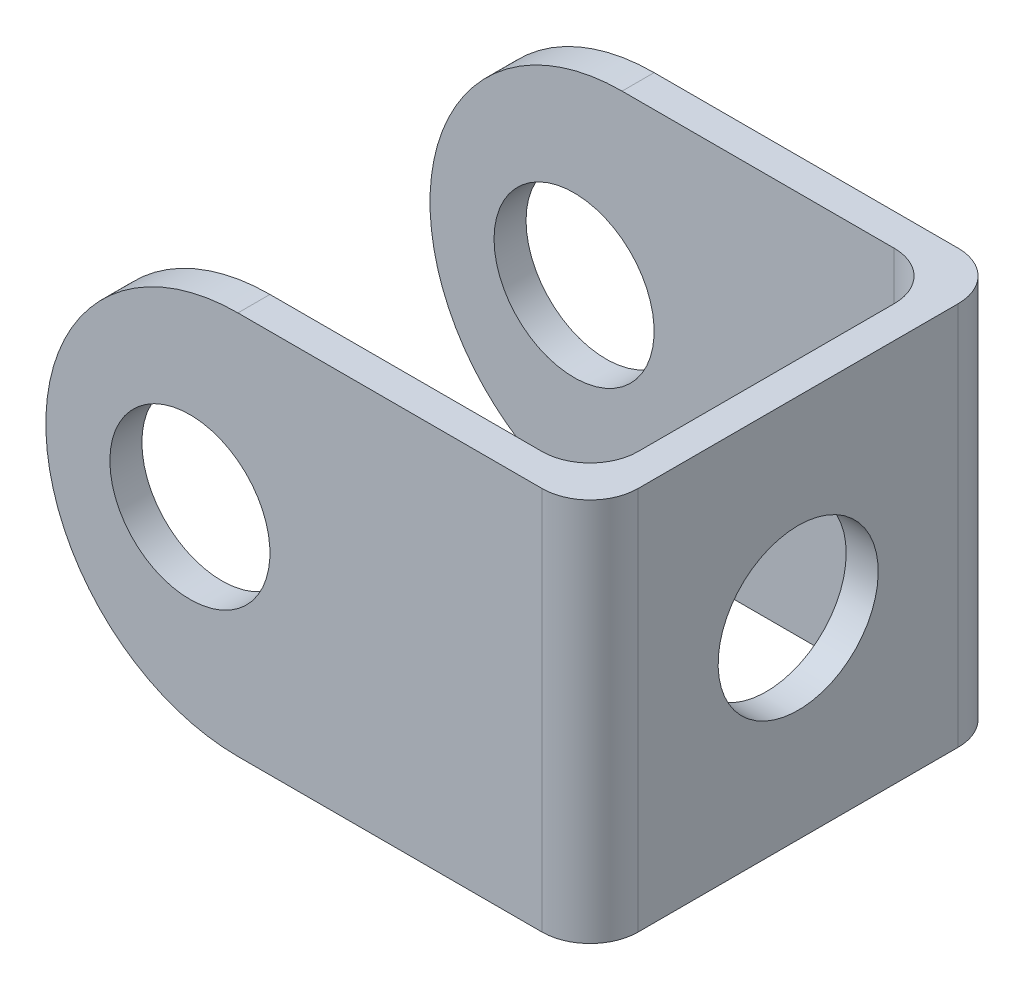
SolidWorks part; units mm, degrees
material "1023 Arkusz stali węglowej (SS)"
ref_plane "Płaszczyzna przednia" through (0, 0, 0) normal (0, 0, 1) x (1, 0, 0)
ref_plane "Płaszczyzna górna" through (0, 0, 0) normal (0, 1, 0) x (1, 0, 0)
ref_plane "Płaszczyzna prawa" through (0, 0, 0) normal (1, 0, 0) x (0, 0, -1)
sketch "Szkic1" plane through (0, 0, 0) normal (0, 0, 1) x (1, 0, 0)
  line L0 (3, 12) -> (25, 12)
  line L1 (3, -12) -> (25, -12)
  line L2 (25, 12) -> (25, -12)
  circle A0 centre (0, 0) radius 5
  arc A1 (3, 12) -> (3, -12) centre (3, 0) ccw
  dimension "D1" = 10
  dimension "D2" = 24
  dimension "D3" = 3
  dimension "D4" = 25
extrude "Dodanie-wyciągnięcie1" add sketch "Szkic1" along normal blind 26
sketch "Szkic2" plane through (0, 12, 0) normal (0, 1, 0) x (1, 0, 0)
  line L0 (25, -26) -> (3, -26) construction
  line L1 (23, -24) -> (-18.5755, -24)
  line L2 (23, -24) -> (23, -2)
  line L3 (23, -2) -> (-18.5755, -2)
  line L4 (-18.5755, -24) -> (-18.5755, -2)
  line L5 (25, 0) -> (3, 0) construction
  line L6 (25, -26) -> (25, 0) construction
  dimension "D1" = 2
  dimension "D2" = 2
  dimension "D3" = 2
extrude "Wytnij-wyciągnięcie1" cut sketch "Szkic2" against normal through all
fillet "Zaokrąglenie1" radius 3 4 edges at (23, 0, 24) (23, 0, 2) (25, 0, 0) (25, 0, 26)
sketch "Szkic3" plane through (25, 0, 0) normal (1, 0, 0) x (0, 0, -1)
  line L0 (-23, 12) -> (-3, 12) construction
  line L1 (0, -12) -> (0, 12) construction
  circle A0 centre (-13, 0) radius 5
  dimension "D1" = 12
  dimension "D3" = 10
  dimension "D2" = 13
extrude "Wytnij-wyciągnięcie2" cut sketch "Szkic3" against normal through all
